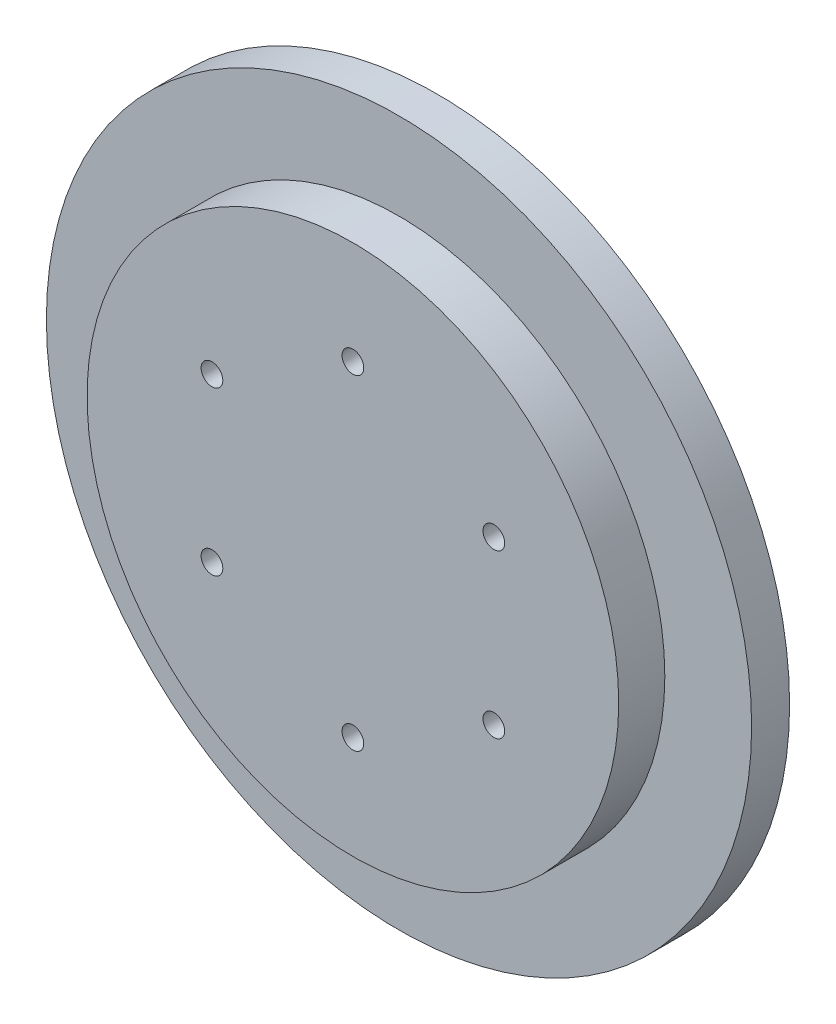
SolidWorks part; units mm, degrees
ref_plane "Front Plane" through (0, 0, 0) normal (0, 0, 1) x (1, 0, 0)
ref_plane "Top Plane" through (0, 0, 0) normal (0, 1, 0) x (1, 0, 0)
ref_plane "Right Plane" through (0, 0, 0) normal (1, 0, 0) x (0, 0, -1)
sketch "Sketch1" plane through (0, 0, 0) normal (0, 0, 1) x (1, 0, 0)
  circle A0 centre (0, 0) radius 49
  dimension "D1" = 98
extrude "Boss-Extrude1" add sketch "Sketch1" along normal blind 8.5
sketch "Sketch3" plane through (0, 0, 0) normal (0, 0, -1) x (-1, 0, 0)
  circle A0 centre (0, 0) radius 65
  dimension "D1" = 130
extrude "Boss-Extrude2" add sketch "Sketch3" along normal blind 7
sketch "Sketch4" plane through (0, 0, -7) normal (0, 0, -1) x (-1, 0, 0)
  circle A0 centre (0, 0) radius 11
  dimension "D1" = 22
extrude "Cut-Extrude1" cut sketch "Sketch4" against normal blind 7
sketch "Sketch5" plane through (0, 0, 0) normal (0, 0, -1) x (-1, 0, 0)
  circle A0 centre (0, 0) radius 7.5
  dimension "D1" = 15
extrude "Cut-Extrude2" cut sketch "Sketch5" against normal blind 0.5
sketch "Sketch6" plane through (0, 0, 8.5) normal (0, 0, 1) x (1, 0, 0)
  circle A0 centre (0, 30) radius 2
  dimension "D1" = 4
  dimension "D2" = 30
extrude "Cut-Extrude3" cut sketch "Sketch6" against normal blind 8
pattern_circular "CirPattern1" count 6 over 360 about axis through (0, 0, 8.5) along (0, 0, 1) of "Cut-Extrude3"
